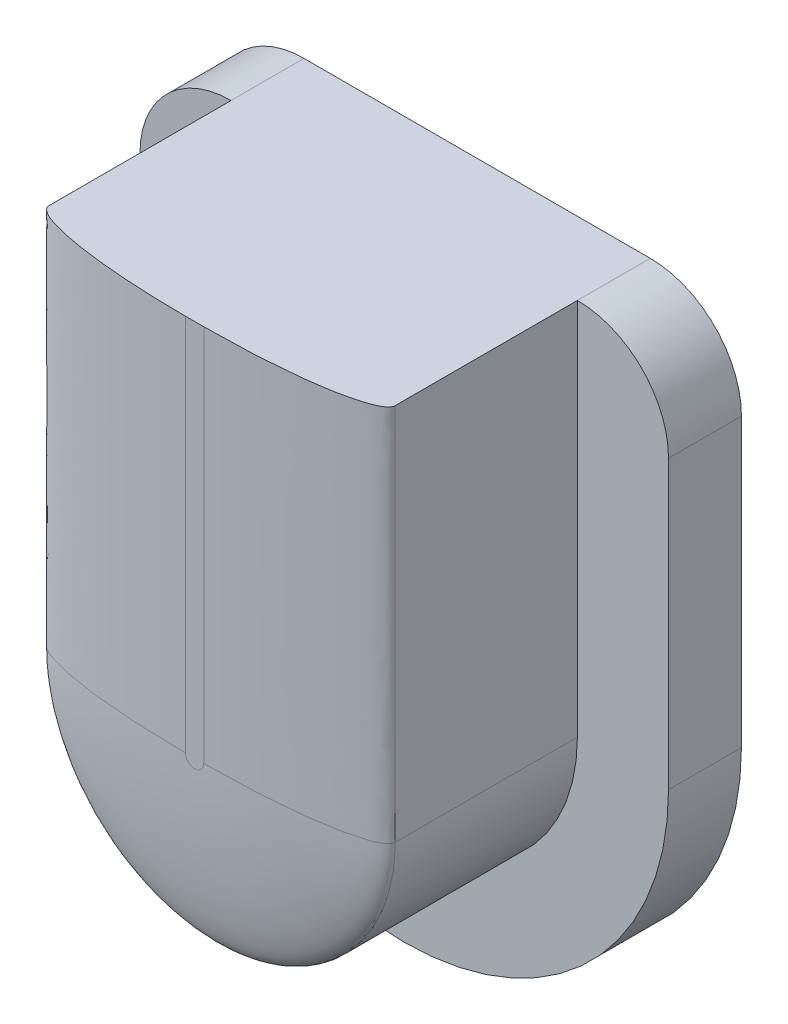
SolidWorks part; units mm, degrees
ref_plane "Front" through (0, 0, 0) normal (0, 0, 1) x (1, 0, 0)
ref_plane "Top" through (0, 0, 0) normal (0, 1, 0) x (1, 0, 0)
ref_plane "Right" through (0, 0, 0) normal (1, 0, 0) x (0, 0, -1)
sketch "草图1" plane through (0, 0, 0) normal (0, 0, 1) x (1, 0, 0)
  line L0 (0.6, -78.273) -> (0.6, -61.673) construction
  line L1 (-1.3, -78.273) -> (-1.3, -61.673)
  line L2 (2.5, -78.273) -> (2.5, -61.673)
  arc A0 (-1.3, -78.273) -> (2.5, -78.273) centre (0.6, -78.273) ccw
  arc A1 (2.5, -61.673) -> (-1.3, -61.673) centre (0.6, -61.673) ccw
  point P4 (0.6, -69.973)
  dimension "D1" = 3.8
extrude "凸台-拉伸1" add sketch "草图1" along normal blind 3.1
sketch "草图2" plane through (0, 0, 0) normal (0, 0, -1) x (-1, 0, 0)
  line L8 (2.3, -78.273) -> (2.3, -61.673)
  line L9 (-3.5, -61.673) -> (-3.5, -78.273)
  line L10 (2.3, -78.273) -> (2.3, -61.673)
  line L11 (-3.5, -61.673) -> (-3.5, -78.273)
  arc A8 (-3.5, -78.273) -> (2.3, -78.273) centre (-0.6, -78.273) ccw
  arc A9 (2.3, -61.673) -> (-3.5, -61.673) centre (-0.6, -61.673) ccw
  arc A10 (-3.5, -78.273) -> (2.3, -78.273) centre (-0.6, -78.273) ccw
  arc A11 (2.3, -61.673) -> (-3.5, -61.673) centre (-0.6, -61.673) ccw
  dimension "D1" = 1
extrude "凸台-拉伸2" add sketch "草图2" against normal blind 0.8
ref_plane "基准面1" through (0, 0, 3.1) normal (0, 0, 1) x (1, 0, 0)
fillet "圆角1" radius 0.3 4 edges at (2.5, -69.973, 3.1) (0.6, -59.773, 3.1) (0.6, -80.173, 3.1) (-1.3, -69.973, 3.1) second distance 1.8 first distance on face at (2.5, -69.973, 1.95) first distance on face at (0.6, -60.723, 1.95) first distance on face at (0.6, -79.223, 1.95) first distance on face at (-1.3, -69.973, 1.95)
sketch "草图3" plane through (0, 0, 0) normal (0, 0, -1) x (-1, 0, 0)
  line L0 (-0.6, -61.673) -> (-0.6, -78.273) construction
  circle A0 centre (-0.6, -61.673) radius 1
  circle A1 centre (-0.6, -69.973) radius 1.0967
  circle A2 centre (-0.6, -78.273) radius 1.0967
  point P9 (-0.6, -69.973)
  dimension "D1" = 2
extrude "凸台-拉伸3" add sketch "草图3" along normal blind 1.05
sketch "草图6" plane through (0, 0, 0) normal (0, 0, -1) x (-1, 0, 0)
  line L0 (-0.6, -78.273) -> (-0.6, -69.973) construction
  line L1 (-0.6, -69.973) -> (-0.6, -61.673) construction
  line L2 (-3.5, -61.673) -> (-3.5, -78.273) construction
  line L3 (2.3, -75.273) -> (-3.5, -75.273)
  line L4 (2.3, -75.273) -> (2.3, -72.973)
  line L5 (2.3, -72.973) -> (-3.5, -72.973)
  line L6 (-3.5, -75.273) -> (-3.5, -72.973)
  line L7 (2.3, -75.273) -> (-3.5, -72.973) construction
  line L8 (2.3, -72.973) -> (-3.5, -75.273) construction
  line L10 (2.3, -66.973) -> (-3.5, -66.973)
  line L11 (2.3, -66.973) -> (2.3, -64.673)
  line L12 (2.3, -64.673) -> (-3.5, -64.673)
  line L13 (-3.5, -66.973) -> (-3.5, -64.673)
  line L14 (2.3, -66.973) -> (-3.5, -64.673) construction
  line L15 (2.3, -64.673) -> (-3.5, -66.973) construction
  point P4 (-0.6, -74.123)
  point P13 (-0.6, -65.823)
  dimension "D1" = 2.3
fillet "圆角5" radius 0.9 3 edges at (1.6, -61.673, 0) (1.6967, -69.973, 0) (1.6967, -78.273, 0)
sketch "草图5" [suppressed] plane through (0, 0, 3.1) normal (0, 0, 1) x (1, 0, 0)
  line L0 (1.801, -60.7382) -> (1.801, -79.2175) construction
  text T1 "OldGerman" font "DS ISO 1" height 2.6
sketch "草图7" plane through (0, 0, 0) normal (0, 0, -1) x (-1, 0, 0)
  line L5 (-3.5, -61.673) -> (-3.5, -78.273) construction
  line L12 (2.3, -49.223) -> (-3.5, -49.223)
  line L13 (2.3, -49.223) -> (2.3, -74.123)
  line L14 (2.3, -74.123) -> (-3.5, -74.123)
  line L15 (-3.5, -49.223) -> (-3.5, -74.123)
  line L16 (2.3, -49.223) -> (-3.5, -74.123) construction
  line L17 (2.3, -74.123) -> (-3.5, -49.223) construction
  point P0 (-0.6, -69.973)
  point P1 (-3.5, -72.2988)
  point P8 (-0.6, -61.673)
extrude "切除-拉伸2" cut sketch "草图7" against normal through all and the other way through all
fillet "圆角6" radius 1 2 edges at (-2.3, -74.123, 0.4) (3.5, -74.123, 0.4)
